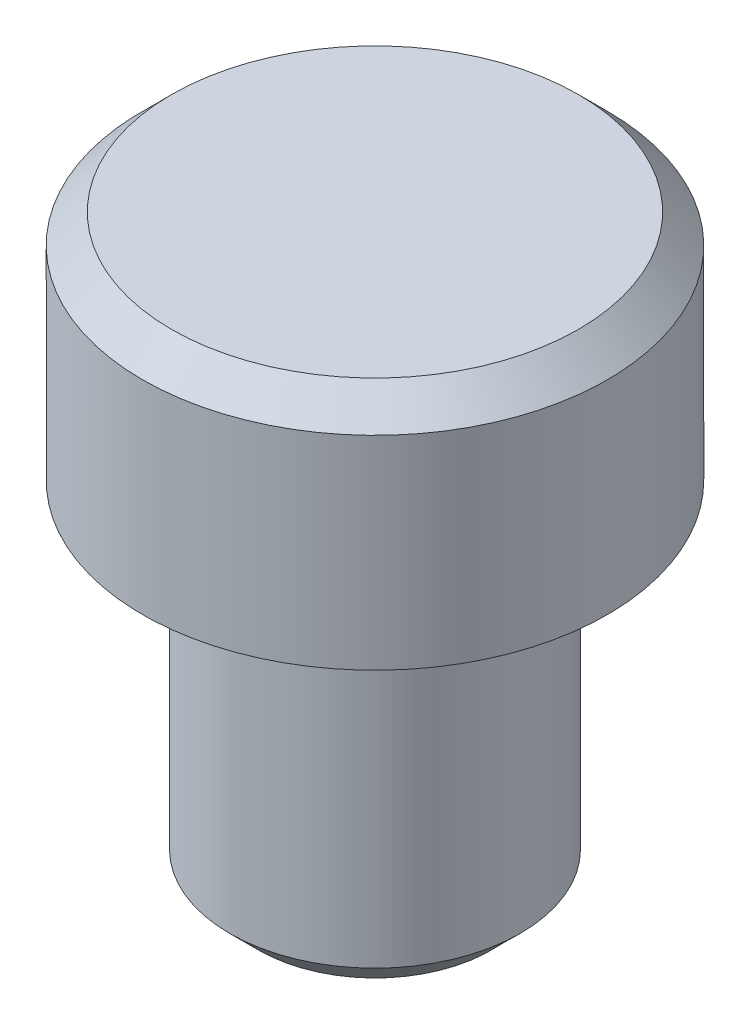
SolidWorks part; units mm, degrees
material "AISI 304"
ref_plane "前视基准面" through (0, 0, 0) normal (0, 0, 1) x (1, 0, 0)
ref_plane "上视基准面" through (0, 0, 0) normal (0, 1, 0) x (1, 0, 0)
ref_plane "右视基准面" through (0, 0, 0) normal (1, 0, 0) x (0, 0, -1)
sketch "草图1" plane through (0, 0, 0) normal (0, 0, 1) x (1, 0, 0)
  line L0 (0, 0) -> (8, 0)
  line L1 (8, 0) -> (8, -8)
  line L2 (8, -8) -> (4, -8)
  line L3 (4, -8) -> (4, -9)
  line L4 (4, -9) -> (5, -9)
  line L5 (5, -9) -> (5, -20)
  line L6 (5, -20) -> (0, -20)
  line L7 (0, -20) -> (0, 0)
  dimension "D1" = 8
  dimension "D2" = 8
  dimension "D3" = 20
  dimension "D4" = 5
  dimension "D5" = 1
  dimension "D6" = 1
revolve "旋转1" add sketch "草图1" angle 360 about L7
chamfer "倒角1" distance 1 angle 45 3 edges at (0, -20, -5) (0, 0, -8) (0, -9, -5)
